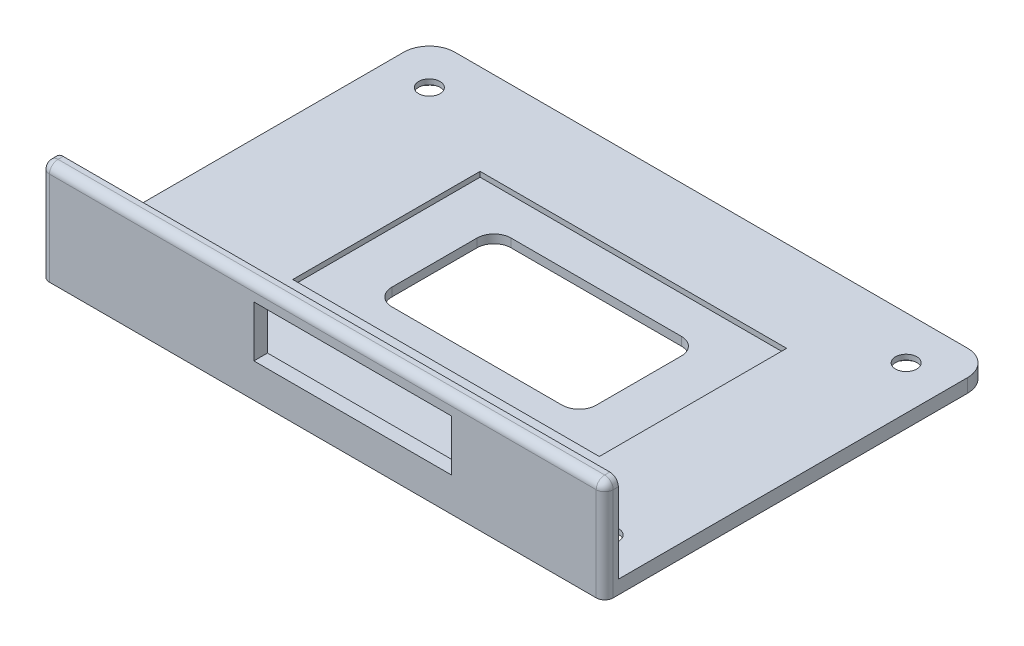
SolidWorks part; units mm, degrees
ref_plane "前视基准面" through (0, 0, 0) normal (0, 0, 1) x (1, 0, 0)
ref_plane "上视基准面" through (0, 0, 0) normal (0, 1, 0) x (1, 0, 0)
ref_plane "右视基准面" through (0, 0, 0) normal (1, 0, 0) x (0, 0, -1)
sketch "草图1" plane through (0, 0, 0) normal (0, 1, 0) x (1, 0, 0)
  line L1 (-33.1, -22) -> (33.1, -22)
  line L2 (-33.1, -22) -> (-33.1, 19)
  line L3 (-30.1, 22) -> (30.1, 22)
  line L4 (33.1, -22) -> (33.1, 19)
  line L5 (-33.1, -22) -> (33.1, 22) construction
  line L6 (-33.1, 22) -> (33.1, -22) construction
  arc A0 (30.1, 22) -> (33.1, 19) centre (30.1, 19) cw
  arc A1 (-33.1, 19) -> (-30.1, 22) centre (-30.1, 19) cw
  point P0 (0, 0)
  dimension "D3" = 3
  dimension "D1" = 44
  dimension "D2" = 66.2
extrude "凸台-拉伸1" add sketch "草图1" along normal blind 1.6
sketch "草图2" plane through (0, 0, 22) normal (0, 0, 1) x (1, 0, 0)
  line L0 (-33.1, 0) -> (33.1, 0)
  line L1 (-33.1, 0) -> (-33.1, 11)
  line L2 (33.1, 0) -> (33.1, 11)
  line L3 (-32.1, 12) -> (-9.1, 12)
  line L5 (-8.1, 10) -> (-8.1, 4)
  line L6 (15.1, 10) -> (15.1, 4)
  line L7 (-8.1, 4) -> (15.1, 4)
  line L8 (17.1, 12) -> (32.1, 12)
  line L9 (-9.1, 12) -> (17.1, 12)
  line L12 (-8.1, 10) -> (15.1, 10)
  arc A0 (33.1, 11) -> (32.1, 12) centre (32.1, 11) ccw
  arc A1 (-33.1, 11) -> (-32.1, 12) centre (-32.1, 11) cw
  point P10 (-33.1, 12)
  point P11 (0, 0)
  dimension "D2" = 1
  dimension "D1" = 12
  dimension "D3" = 8
  dimension "D4" = 25
  dimension "D5" = 18
  dimension "D6" = 6
extrude "封底" add sketch "草图2" along normal blind 1.6
sketch "草图3" plane through (0, 1.6, 0) normal (0, 1, 0) x (1, 0, 0)
  line L1 (-8.5, -7) -> (11.5, -7)
  line L2 (-10.5, -5) -> (-10.5, 5)
  line L3 (-8.5, 7) -> (11.5, 7)
  line L4 (13.5, -5) -> (13.5, 5)
  line L5 (-10.5, -7) -> (13.5, 7) construction
  line L6 (-10.5, 7) -> (13.5, -7) construction
  line L7 (-33.1, -22) -> (33.1, -22) construction
  line L8 (33.1, -22) -> (33.1, 19) construction
  arc A0 (11.5, -7) -> (13.5, -5) centre (11.5, -5) ccw
  arc A1 (-8.5, -7) -> (-10.5, -5) centre (-8.5, -5) cw
  arc A2 (11.5, 7) -> (13.5, 5) centre (11.5, 5) cw
  arc A3 (-10.5, 5) -> (-8.5, 7) centre (-8.5, 5) cw
  point P0 (0, 0)
  dimension "D3" = 2
  dimension "D1" = 24
  dimension "D2" = 14
  dimension "D4" = 19.6
  dimension "D5" = 15
extrude "磁带窗" cut sketch "草图3" against normal up to next
sketch "草图5" plane through (0, 0, 0) normal (0, -1, 0) x (1, 0, 0)
  line L0 (-33.1, -19) -> (-33.1, 23.6) construction
  line L1 (30.1, -22) -> (-30.1, -22) construction
  circle A0 centre (-28, -16.9) radius 2.6
  circle A1 centre (28, -16.9) radius 2.6
  circle A2 centre (28, 18.1) radius 2.6
  circle A3 centre (-28, 18.1) radius 2.6
  point P0 (-28, -16.9)
  point P10 (28, -16.9)
  point P13 (28, 18.1)
  point P16 (-28, 18.1)
  dimension "D3" = 5.2
  dimension "D1" = 5.1
  dimension "D2" = 5.1
  dimension "D4" = 2
  dimension "D5" = 2
extrude "正螺丝孔" cut sketch "草图5" against normal blind 1
sketch "草图7" plane through (0, 1, 0) normal (0, -1, 0) x (1, 0, 0)
  circle A0 centre (-28, -16.9) radius 1.25
  circle A1 centre (28, -16.9) radius 1.25
  circle A2 centre (28, 18.1) radius 1.25
  circle A3 centre (-28, 18.1) radius 1.25
  dimension "D1" = 2.5
  dimension "D2" = 2
  dimension "D3" = 2
extrude "背螺丝孔" cut sketch "草图7" against normal up to next
sketch "草图9" plane through (0, 1.6, 0) normal (0, 1, 0) x (1, 0, 0)
  line L1 (-16.4991, -10.6372) -> (19.5009, -10.6372)
  line L2 (-16.4991, -10.6372) -> (-16.4991, 11.3628)
  line L3 (-16.4991, 11.3628) -> (19.5009, 11.3628)
  line L4 (19.5009, -10.6372) -> (19.5009, 11.3628)
  line L5 (-16.4991, -10.6372) -> (19.5009, 11.3628) construction
  line L6 (-16.4991, 11.3628) -> (19.5009, -10.6372) construction
  point P0 (1.5009, 0.3628)
  dimension "D1" = 36
  dimension "D2" = 22
extrude "屏幕槽" cut sketch "草图9" against normal blind 0.6 contours L2 L1 L4 L3
fillet "圆角2" radius 1 5 edges at (33.1, 5.5, 23.6) (32.8071, 11.7071, 23.6) (-33.1, 5.5, 23.6) (-32.8071, 11.7071, 23.6) (0, 12, 23.6)
